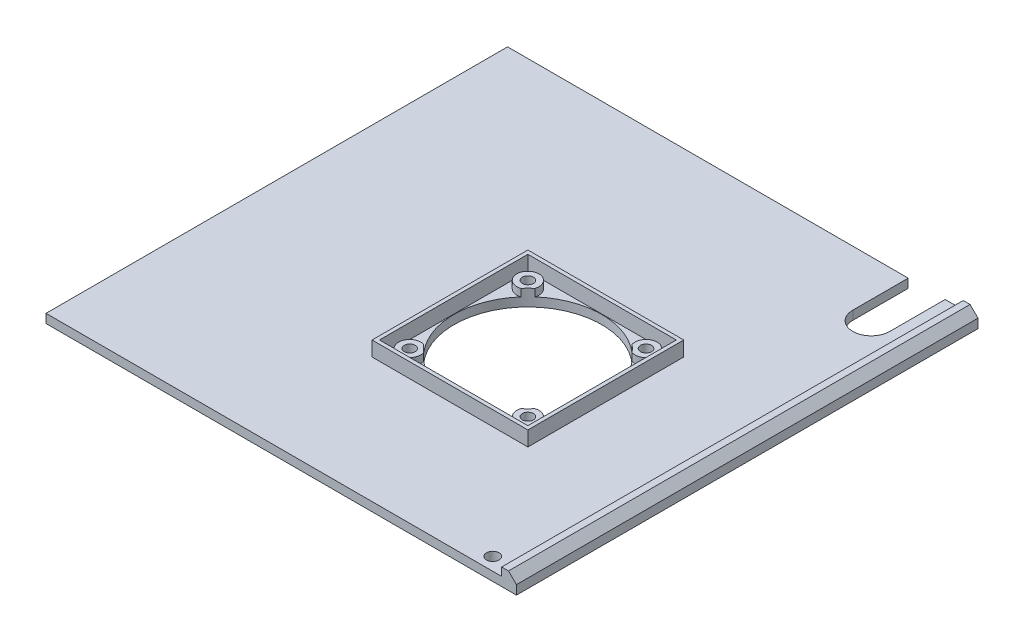
SolidWorks part; units mm, degrees
material "ABS"
ref_plane "Front Plane" through (0, 0, 0) normal (0, 0, 1) x (1, 0, 0)
ref_plane "Top Plane" through (0, 0, 0) normal (0, 1, 0) x (1, 0, 0)
ref_plane "Right Plane" through (0, 0, 0) normal (1, 0, 0) x (0, 0, -1)
ref_axis "Axis1" through (0, 0, 55) along (0, 0, -1)
sketch "Sketch1" plane through (0, 0, 0) normal (0, 1, 0) x (1, 0, 0)
  line L1 (-60.75, 62.5) -> (60.75, 62.5)
  line L2 (-60.75, 62.5) -> (-60.75, -62.5)
  line L3 (-60.75, -62.5) -> (60.75, -62.5)
  line L4 (60.75, 62.5) -> (60.75, -62.5)
  line L5 (-60.75, 62.5) -> (60.75, -62.5) construction
  line L6 (-60.75, -62.5) -> (60.75, 62.5) construction
  point P0 (0, 0)
  dimension "D1" = 121.5
  dimension "D2" = 125
extrude "Boss-Extrude1" add sketch "Sketch1" along normal blind 2.4
sketch "4040-extrusion" plane through (0, 0, 62.5) normal (0, 0, 1) x (1, 0, 0)
  line L0 (60.75, 0) -> (60.75, 9.5) construction
  line L1 (60.75, 9.5) -> (60.75, 4.3) construction
  line L2 (60.75, 4.3) -> (62.55, 2.5) construction
  line L3 (62.55, 2.5) -> (62.55, 4.71) construction
  line L4 (62.55, 4.71) -> (64.55, 4.71) construction
  line L5 (64.55, 4.71) -> (66.75, 2.5118) construction
  line L6 (66.75, 2.5118) -> (66.75, 0) construction
  dimension "D1" = 9.5
  dimension "D2" = 5.2
  dimension "D3" = 7
  dimension "D4" = 1.8
  dimension "D5" = 2
  dimension "D6" = 3.11
  dimension "D7" = 2.21
  dimension "D8" = 6
sketch "Sketch3" plane through (0, 0, 62.5) normal (0, 0, 1) x (1, 0, 0)
  line L0 (60.75, 0) -> (60.75, 2.4)
  line L1 (60.75, 2.4) -> (62.55, 2.4)
  line L2 (62.55, 2.4) -> (62.55, 4.71) construction
  line L3 (62.55, 4.71) -> (64.55, 4.71) construction
  line L4 (64.55, 4.71) -> (66.75, 2.5118) construction
  line L5 (66.75, 2.5118) -> (66.75, 0) construction
  line L6 (66.75, 0) -> (66.65, 0) construction
  line L7 (62.65, 2.4) -> (62.65, 4.61)
  line L8 (62.65, 4.61) -> (64.5086, 4.61)
  line L9 (64.5086, 4.61) -> (66.65, 2.4704)
  line L10 (66.65, 2.4704) -> (66.65, 0)
  line L11 (62.55, 2.4) -> (62.65, 2.4)
  line L12 (66.65, 0) -> (60.75, 0)
  dimension "D1" = 0.1
extrude "Boss-Extrude2" add sketch "Sketch3" against normal up to surface (125 mm away) up to face at (0, 1.2, -62.5)
sketch "Sketch4" plane through (0, 2.4, 0) normal (0, 1, 0) x (1, 0, 0)
  line L0 (-60.75, -62.5) -> (62.65, -62.5) construction
  line L1 (53.25, -62.5) -> (60.25, -62.5) construction
  line L2 (53.25, -62.5) -> (53.25, -55.5) construction
  line L3 (53.25, -55.5) -> (60.25, -55.5) construction
  line L4 (60.25, -62.5) -> (60.25, -55.5) construction
  line L5 (53.25, -62.5) -> (60.25, -55.5) construction
  line L6 (53.25, -55.5) -> (60.25, -62.5) construction
  line L7 (56.75, -59) -> (62.65, -59) construction
  line L9 (62.65, 62.5) -> (62.65, -62.5) construction
  circle A0 centre (56.75, -59) radius 1.7
  point P4 (56.75, -59)
  dimension "D2" = 3.4
  dimension "D1" = 7
  dimension "D3" = 5.9
extrude "Cut-Extrude1" cut sketch "Sketch4" against normal through all
sketch "Sketch5" plane through (0, 2.4, 0) normal (0, 1, 0) x (1, 0, 0)
  line L0 (52.75, 62.5) -> (52.75, 47.5) construction
  line L1 (62.65, 62.5) -> (-60.75, 62.5) construction
  line L2 (57.75, 62.5) -> (57.75, 47.5)
  line L3 (47.75, 62.5) -> (47.75, 47.5)
  line L4 (52.75, 55) -> (62.65, 55) construction
  line L6 (47.75, 62.5) -> (57.75, 62.5)
  line L7 (62.65, 62.5) -> (62.65, -62.5) construction
  arc A0 (57.75, 62.5) -> (47.75, 62.5) centre (52.75, 62.5) ccw
  arc A1 (47.75, 47.5) -> (57.75, 47.5) centre (52.75, 47.5) ccw
  point P4 (52.75, 55)
  line M7 (62.65, 62.5) -> (-60.75, 62.5)
  dimension "D1" = 15
  dimension "D2" = 5
  dimension "D3" = 9.9
extrude "Cut-Extrude2" cut sketch "Sketch5" against normal through all contours L3 A1 L2 M7 region at (52.75, 2.4, -53.0036)
sketch "Sketch6" plane through (0, 2.4, 0) normal (0, 1, 0) x (1, 0, 0)
  line L0 (14.75, -7.5) -> (14.75, -62.5) construction
  line L1 (-5.25, 12.5) -> (34.75, 12.5) construction
  line L2 (-5.25, 12.5) -> (-5.25, -27.5) construction
  line L3 (-5.25, -27.5) -> (34.75, -27.5) construction
  line L4 (34.75, 12.5) -> (34.75, -27.5) construction
  line L5 (-5.25, 12.5) -> (34.75, -27.5) construction
  line L6 (-5.25, -27.5) -> (34.75, 12.5) construction
  line L7 (-60.75, -62.5) -> (60.75, -62.5) construction
  line L8 (14.75, -7.5) -> (60.75, -7.5) construction
  line L9 (60.75, 62.5) -> (60.75, -62.5) construction
  line L11 (-1.25, 8.5) -> (30.75, 8.5) construction
  line L12 (-1.25, 8.5) -> (-1.25, -23.5) construction
  line L13 (-1.25, -23.5) -> (30.75, -23.5) construction
  line L14 (30.75, 8.5) -> (30.75, -23.5) construction
  line L15 (-1.25, 8.5) -> (30.75, -23.5) construction
  line L16 (-1.25, -23.5) -> (30.75, 8.5) construction
  circle A0 centre (-1.25, -23.5) radius 1.5
  circle A1 centre (30.75, -23.5) radius 1.5
  circle A2 centre (30.75, 8.5) radius 1.5
  circle A3 centre (-1.25, 8.5) radius 1.5
  circle A4 centre (14.75, -7.5) radius 20 construction
  point P0 (14.75, -7.5)
  dimension "D4" = 3
  dimension "D1" = 46
  dimension "D2" = 55
  dimension "D3" = 40
  dimension "D5" = 32
extrude "Cut-Extrude3" cut sketch "Sketch6" against normal through all
sketch "Sketch7" plane through (0, 2.4, 0) normal (0, 1, 0) x (1, 0, 0)
  line L0 (14.7563, -7.5) -> (14.7563, 12.4937) construction
  line L1 (14.7563, -7.5) -> (21.4208, -7.5) construction
  line L2 (21.4208, -7.5) -> (28.0854, -7.5) construction
  line L3 (28.0854, -7.5) -> (34.75, -7.5) construction
  line L4 (28.0854, -7) -> (34.75, -7)
  line L5 (21.4208, -7) -> (28.0854, -7)
  line L6 (15.2563, -7) -> (21.4208, -7)
  line L7 (15.2563, -7) -> (15.2563, 12.4937)
  line L8 (34.75, 12.5) -> (34.75, -27.5) construction
  line L9 (14.75, -7.5) -> (60.75, -7.5) construction
  arc A2 (14.7563, -0.8354) -> (21.4208, -7.5) centre (14.7563, -7.5) cw construction
  arc A3 (14.7563, 5.8292) -> (28.0854, -7.5) centre (14.7563, -7.5) cw construction
  arc A4 (14.7563, -1.3354) -> (20.9208, -7.5) centre (14.7563, -7.5) cw
  arc A5 (14.7563, 5.3292) -> (27.5854, -7.5) centre (14.7563, -7.5) cw
  arc A6 (14.7563, -0.3354) -> (21.9208, -7.5) centre (14.7563, -7.5) cw
  arc A7 (14.7563, 6.3292) -> (28.5854, -7.5) centre (14.7563, -7.5) cw
  arc A8 (15.2563, 12.4937) -> (34.75, -7) centre (14.7563, -7.5) cw
  circle A9 centre (14.75, -7.5) radius 20 construction
  arc A10 (14.7563, -1.3354) -> (20.9208, -7.5) centre (14.7563, -7.5) cw construction
  dimension "D1" = 0.5
  dimension "D2" = 0.5
  dimension "D3" = 0.5
extrude "Cut-Extrude4" [suppressed] cut sketch "Sketch7" against normal through all contours A4 L7 L6 | L7 A6 L5 A5 | A8 L7 A7 L4
pattern_circular "CirPattern1" [suppressed] count 4 every 90 of bodies 106
sketch "Sketch8" plane through (0, 2.4, 0) normal (0, 1, 0) x (1, 0, 0)
  circle A0 centre (14.75, -7.5) radius 20 construction
  circle A1 centre (14.75, -7.5) radius 20
extrude "Cut-Extrude5" cut sketch "Sketch8" against normal through all
sketch "Sketch9" plane through (0, 2.4, 0) normal (0, 1, 0) x (1, 0, 0)
  circle A0 centre (-1.25, -23.5) radius 1.5 construction
  circle A1 centre (30.75, -23.5) radius 1.5 construction
  circle A2 centre (30.75, 8.5) radius 1.5 construction
  circle A3 centre (-1.25, 8.5) radius 1.5 construction
  circle A4 centre (-1.25, -23.5) radius 1.5
  circle A5 centre (30.75, -23.5) radius 1.5
  circle A6 centre (30.75, 8.5) radius 1.5
  circle A7 centre (-1.25, 8.5) radius 1.5
  arc A8 (1.6027, 7.5714) -> (-0.3214, 5.6473) centre (-1.25, 8.5) ccw
  arc A9 (29.8214, 5.6473) -> (27.8973, 7.5714) centre (30.75, 8.5) ccw
  arc A10 (27.8973, -22.5714) -> (29.8214, -20.6473) centre (30.75, -23.5) ccw
  arc A11 (-0.3214, -20.6473) -> (1.6027, -22.5714) centre (-1.25, -23.5) ccw
  circle A12 centre (14.75, -7.5) radius 20 construction
  arc A13 (1.6027, 7.5714) -> (-0.3214, 5.6473) centre (14.75, -7.5) ccw
  circle A14 centre (-1.25, 8.5) radius 3 construction
  circle A15 centre (30.75, 8.5) radius 3 construction
  arc A16 (29.8214, 5.6473) -> (27.8973, 7.5714) centre (14.75, -7.5) ccw
  circle A17 centre (30.75, -23.5) radius 3 construction
  arc A18 (27.8973, -22.5714) -> (29.8214, -20.6473) centre (14.75, -7.5) ccw
  circle A19 centre (-1.25, -23.5) radius 3 construction
  arc A20 (-0.3214, -20.6473) -> (1.6027, -22.5714) centre (14.75, -7.5) ccw
  dimension "D1" = 1.5
extrude "Boss-Extrude3" add sketch "Sketch9" along normal blind 2
sketch "Sketch10" plane through (0, 2.4, 0) normal (0, 1, 0) x (1, 0, 0)
  line L0 (-5.25, 12.5) -> (-5.25, -27.5) construction
  line L1 (-5.25, -27.5) -> (34.75, -27.5) construction
  line L2 (34.75, 12.5) -> (34.75, -27.5) construction
  line L3 (-5.25, 12.5) -> (34.75, 12.5) construction
  line L4 (-5.25, 12.5) -> (-5.25, -27.5) construction
  line L5 (-5.25, -27.5) -> (34.75, -27.5) construction
  line L6 (34.75, 12.5) -> (34.75, -27.5) construction
  line L7 (-5.25, 12.5) -> (34.75, 12.5) construction
  line L8 (-5.35, 12.6) -> (34.85, 12.6)
  line L9 (34.85, 12.6) -> (34.85, -27.6)
  line L10 (-5.35, -27.6) -> (34.85, -27.6)
  line L11 (-5.35, 12.6) -> (-5.35, -27.6)
  line L12 (-6.35, 13.6) -> (35.85, 13.6)
  line L13 (35.85, 13.6) -> (35.85, -28.6)
  line L14 (-6.35, -28.6) -> (35.85, -28.6)
  line L15 (-6.35, 13.6) -> (-6.35, -28.6)
  dimension "D1" = 0.1
  dimension "D2" = 1
extrude "Boss-Extrude4" add sketch "Sketch10" along normal blind 4
